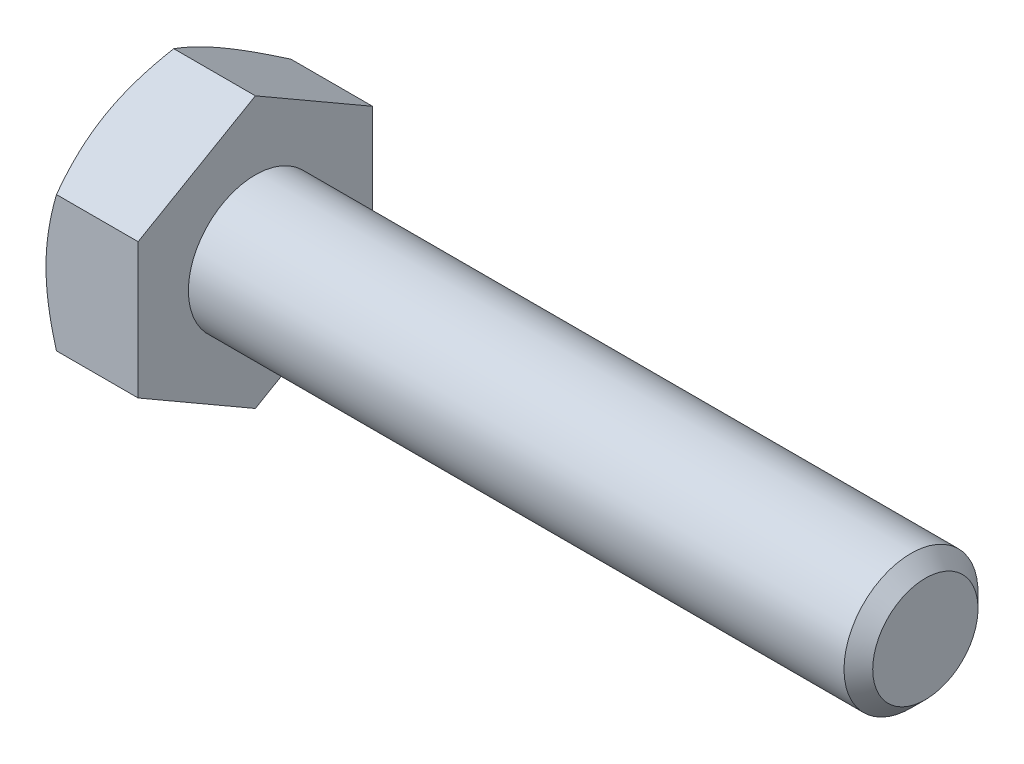
SolidWorks part; units mm, degrees
material "Alloy Steel"
ref_plane "Front Plane" through (0, 0, 0) normal (0, 0, 1) x (1, 0, 0)
ref_plane "Top Plane" through (0, 0, 0) normal (0, 1, 0) x (1, 0, 0)
ref_plane "Right Plane" through (0, 0, 0) normal (1, 0, 0) x (0, 0, -1)
sketch "Sketch1" plane through (0, 0, 0) normal (0, 0, 1) x (1, 0, 0)
  line L0 (-18.0578, 0) -> (18.0578, 0) construction
  line L1 (18.0578, 3.175) -> (18.0578, -3.175) construction
  line L2 (-13.6922, 5.5562) -> (-13.6922, -5.5562) construction
  line L3 (-18.0578, 5.5562) -> (-18.0578, -5.5562) construction
  point P9 (-13.6922, 0)
  point P10 (14.8828, -3.175)
  dimension "Screw Dia" = 6.35
  dimension "Hex" = 11.1125
  dimension "Head Ht" = 4.3656
  dimension "Screw Lenght" = 31.75
  dimension "D1" = 3.175
ref_plane "Plane2" through (18.0578, 0, 0) normal (1, 0, 0) x (0, 0, -1)
sketch "Sketch5" plane through (18.0578, 0, 0) normal (1, 0, 0) x (0, 0, -1)
  circle A0 centre (0, 0) radius 3.175
extrude "Boss-Extrude3" add sketch "Sketch5" against normal up to vertex (31.75 mm away) up to point (-13.6922, 0, 0)
sketch "Sketch9" plane through (18.0578, 0, 0) normal (1, 0, 0) x (0, 0, -1)
  circle A1 centre (0, 0) radius 3.175
  circle A2 centre (0, 0) radius 3.175
  dimension "D1" = 0
curve "Helix/Spiral1" [suppressed] pitch 0.9071 height 19.9571 turns 22 parameters "Pitch"=0.9071
chamfer "Chamfer1" distance 0.6804 angle 45 1 edges at (18.0578, 0, -3.175)
sketch "Sketch10" plane through (0, 0, 0) normal (0, 0, 1) x (1, 0, 0)
  line L0 (18.0578, 3.175) -> (18.398, 2.5858)
  line L1 (18.398, 2.5858) -> (18.5114, 2.5858)
  line L2 (18.5114, 2.5858) -> (18.8516, 3.175)
  line L3 (18.0578, 3.175) -> (18.8516, 3.175)
  line L4 (18.4547, 3.175) -> (18.4547, 2.5858) construction
  line L5 (18.2279, 2.8804) -> (18.6815, 2.8804) construction
  dimension "D1" = 60
  dimension "D2" = 0.1134
  dimension "D3" = 0.4536
sweep "Cut-Sweep1" [suppressed] cut profiles "Sketch10" path "Helix/Spiral1"
sketch "Sketch11" plane through (0, 0, 0) normal (0, 0, 1) x (1, 0, 0)
  line L0 (-13.6922, 3.175) -> (-13.6922, 0)
  line L1 (-13.6922, 0) -> (2.1828, 0)
  line L3 (2.1828, 0) -> (-0.9922, 3.175)
  line L4 (-13.6922, 3.175) -> (-0.9922, 3.175)
  dimension "D1" = 45
  dimension "MIn Thread" = 19.05
revolve "Revolve1" [suppressed] add sketch "Sketch11" angle 360 about L1
sketch "Sketch6" plane through (-13.6922, 0, 0) normal (-1, 0, 0) x (0, 0, 1)
  line L0 (0, 5.5562) -> (0, -5.5562) construction
  line L1 (5.5563, 3.2079) -> (0, 6.4158)
  line L2 (0, 6.4158) -> (-5.5562, 3.2079)
  line L3 (-5.5562, 3.2079) -> (-5.5562, -3.2079)
  line L4 (-5.5562, -3.2079) -> (0, -6.4158)
  line L5 (0, -6.4158) -> (5.5563, -3.2079)
  line L6 (5.5563, -3.2079) -> (5.5563, 3.2079)
  circle A0 centre (0, 0) radius 5.5562 construction
extrude "Boss-Extrude4" add sketch "Sketch6" along normal up to vertex (4.3656 mm away) up to point (-18.0578, -5.5562, 0)
sketch "Sketch7" plane through (-18.0578, 0, 0) normal (-1, 0, 0) x (0, 0, 1)
  circle A0 centre (0, 0) radius 5.5562 construction
  circle A1 centre (0, 0) radius 5.5562
sketch "Sketch8" plane through (-18.0578, 0, 0) normal (-1, 0, 0) x (0, 0, 1)
  circle A0 centre (0, 0) radius 5.5562 construction
  circle A1 centre (0, 0) radius 5.5562
extrude "Cut-Extrude3" cut sketch "Sketch8" against normal through all draft 60 flip side to cut
sketch "Sketch12" plane through (-18.0578, 0, 0) normal (-1, 0, 0) x (0, 0, 1)
  line L0 (0, 4.2783) -> (0, 2.3892) construction
  line L1 (0.1667, 4.2783) -> (0.1667, 2.3892)
  line L2 (-0.1667, 4.2783) -> (-0.1667, 2.3892)
  line L3 (0, 3.175) -> (0, -3.175) construction
  arc A0 (0.1667, 4.2783) -> (-0.1667, 4.2783) centre (0, 4.2783) ccw
  arc A1 (-0.1667, 2.3892) -> (0.1667, 2.3892) centre (0, 2.3892) ccw
  circle A3 centre (0, 0) radius 2.2225 construction
  circle A4 centre (0, 0) radius 4.445 construction
  point P2 (0, 3.3337)
  dimension "D1" = 4.445
  dimension "D3" = 8.89
  dimension "D2" = 0.3334
extrude "Cut-Extrude4" [suppressed] cut sketch "Sketch12" against normal blind 0.254
pattern_circular "CirPattern1" [suppressed] count 6 over 360 of bodies 116
equation "\"D2@Sketch10\" = \"Pitch@Helix/Spiral1\"*.125"
equation "\"D3@Sketch10\" = \"Pitch@Helix/Spiral1\"*.5"
equation "\"D3@Helix/Spiral1\" = \"MIn Thread@Sketch11\"+\"Pitch@Helix/Spiral1\""
equation "\"D1@Chamfer1\" = \"Pitch@Helix/Spiral1\"*.75"
equation "\"D1@Sketch12\" = \"Hex@Sketch1\"*.4"
equation "\"D3@Sketch12\" = \"Hex@Sketch1\"*.8"
equation "\"D2@Sketch12\" = \"Hex@Sketch1\"*.03"
equation "\"D1@Sketch1\" = \"Pitch@Helix/Spiral1\"*3.5"
